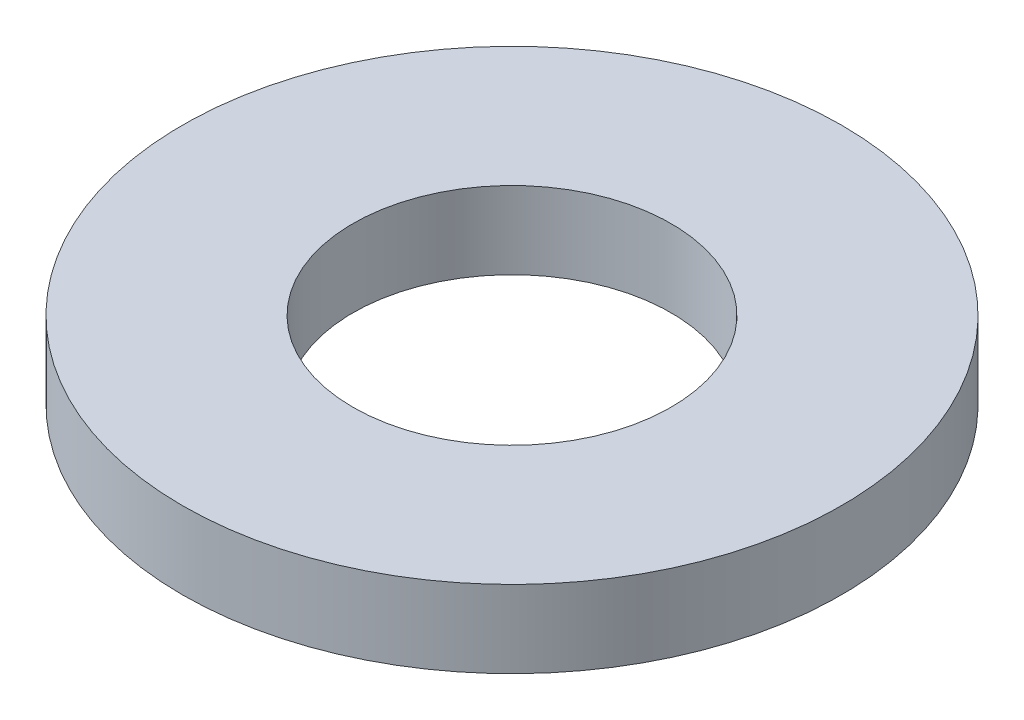
SolidWorks part; units mm, degrees
ref_plane "Front Plane" through (0, 0, 0) normal (0, 0, 1) x (1, 0, 0)
ref_plane "Top Plane" through (0, 0, 0) normal (0, 1, 0) x (1, 0, 0)
ref_plane "Right Plane" through (0, 0, 0) normal (1, 0, 0) x (0, 0, -1)
sketch "Sketch1" plane through (0, 0, 0) normal (0, 1, 0) x (1, 0, 0)
  circle A0 centre (0, 0) radius 72.5
  dimension "FLANGE_OD" = 145
extrude "Boss-Extrude1" add sketch "Sketch1" along normal blind 17
sketch "Sketch2" plane through (0, 0, 0) normal (0, 1, 0) x (1, 0, 0)
  circle A0 centre (0, 0) radius 35
  dimension "BORE_D" = 70
extrude "Cut-Extrude1" cut sketch "Sketch2" along normal through all
sketch "Sketch3" plane through (0, 17, 0) normal (0, 1, 0) x (1, 0, 0)
  circle A0 centre (0, 0) radius 32.9747 construction
  circle A1 centre (-32.9747, 0) radius 1.8354
  dimension "BOLT_D" = 3.6707
  dimension "BOLT_PCD" = 65.9495
extrude "Cut-Extrude2" cut sketch "Sketch3" against normal blind 14.6968 rebuild error yes
pattern_circular "CirPattern1" count 8 over 360 rebuild error yes
